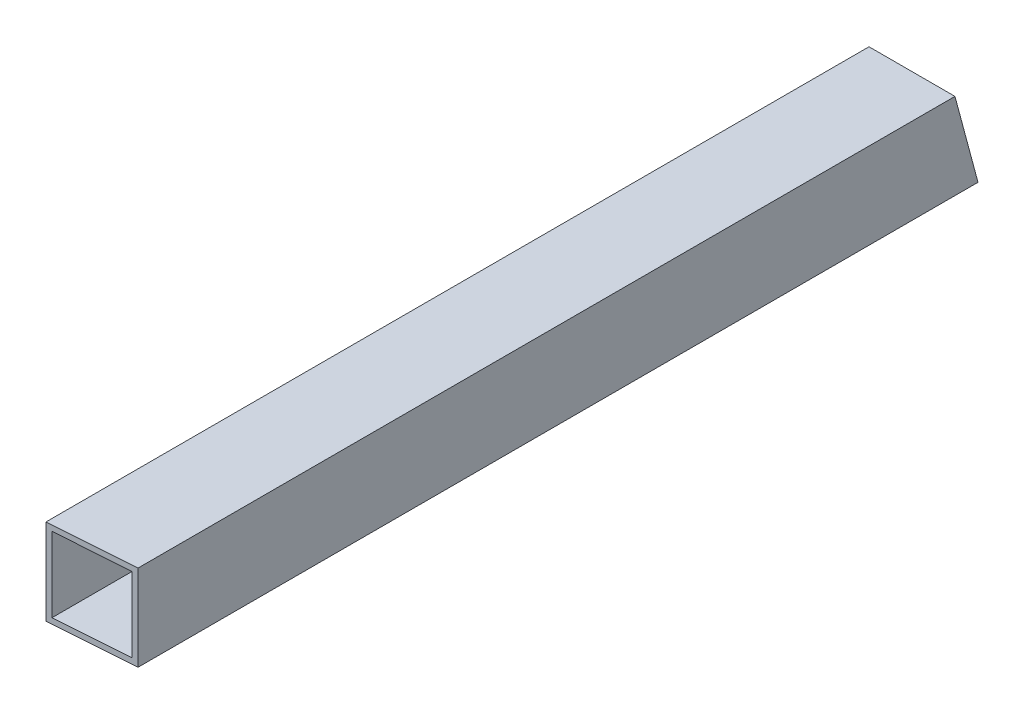
SolidWorks part; units mm, degrees
ref_plane "Front Plane" through (0, 0, 0) normal (0, 0, 1) x (1, 0, 0)
ref_plane "Top Plane" through (0, 0, 0) normal (0, 1, 0) x (1, 0, 0)
ref_plane "Right Plane" through (0, 0, 0) normal (1, 0, 0) x (0, 0, -1)
sketch "Sketch6" plane through (0, 0, 0) normal (0, 0, 1) x (1, 0, 0)
  line L1 (0, 0) -> (25.4, 0)
  line L2 (0, 0) -> (0, -25.4)
  line L3 (0, -25.4) -> (25.4, -25.4)
  line L4 (25.4, 0) -> (25.4, -25.4)
  dimension "D1" = 25.4
  dimension "D2" = 25.4
extrude "Boss-Extrude1" add sketch "Sketch6" along normal blind 250
sketch "Sketch7" plane through (0, 0, 0) normal (0, 1, 0) x (1, 0, 0)
  line L0 (0, -250) -> (25.4, -248.1806)
  line L1 (25.4, -250) -> (25.4, 0) construction
  line L3 (25.4, -248.1806) -> (25.4, -250)
  line L4 (0, -250) -> (0, 0) construction
  line L5 (25.4, -250) -> (0, -250)
  dimension "D1" = 85.903
extrude "Cut-Extrude2" cut sketch "Sketch7" against normal through all
shell "Shell1" thickness 1.651 removed face at (12.7, -12.7, 249.0903) removed face at (12.7, -12.7, 0)
sketch "Sketch10" plane through (0, 0, 0) normal (-1, 0, 0) x (0, 0, 1)
  line L0 (0, -25.4) -> (6.8059, 0)
  line L1 (250, 0) -> (0, 0) construction
  line L2 (6.8059, 0) -> (0, 0)
  line L3 (0, 0) -> (0, -25.4)
  dimension "D1" = 15
extrude "Cut-Extrude3" cut sketch "Sketch10" against normal through all
equation "\"A\"=250"
equation "\"t1len\"=250"
equation "\"D1@Boss-Extrude1\"=\"t1len\""
equation "\"D1@Sketch7\"= ( 180 - atn ( 36 / 250 ) ) / 2"
